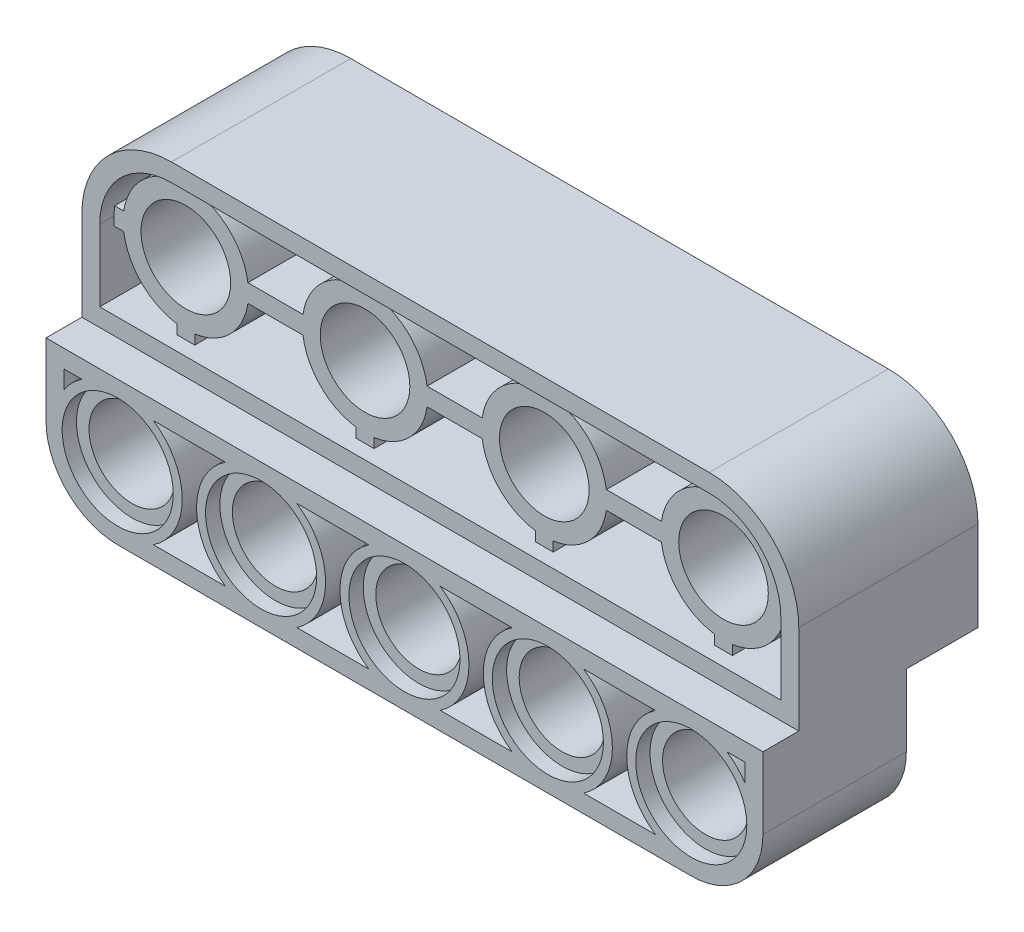
SolidWorks part; units mm, degrees
ref_plane "Front Plane" through (0, 0, 0) normal (0, 0, 1) x (1, 0, 0)
ref_plane "Top Plane" through (0, 0, 0) normal (0, 1, 0) x (1, 0, 0)
ref_plane "Right Plane" through (0, 0, 0) normal (1, 0, 0) x (0, 0, -1)
sketch "Sketch1" plane through (0, 0, 0) normal (1, 0, 0) x (0, 0, -1)
  line L0 (-5, -5) -> (-5, -13)
  line L1 (5, 5) -> (-5, 5)
  line L2 (5, 5) -> (5, -5)
  line L3 (5, -5) -> (-5, -5)
  line L4 (-5, 5) -> (-5, -5)
  line L5 (5, 5) -> (-5, -5) construction
  line L6 (5, -5) -> (-5, 5) construction
  line L7 (-5, -13) -> (3, -13)
  line L8 (3, -13) -> (3, -5)
  point P0 (0, 0)
  dimension "D1" = 10
  dimension "D2" = 10
  dimension "D3" = 8
  dimension "D4" = 8
extrude "Boss-Extrude1" add sketch "Sketch1" along normal blind 40 contours L1 L4 L3 L2 | L7 L8 L3 L0 region at (0, -9, 1) region at (0, 0, 0)
sketch "Sketch2" plane through (0, 0, -5) normal (0, 0, -1) x (-1, 0, 0)
  line L0 (-40, 0) -> (0, 0) construction
  line L1 (-40, 5) -> (-40, -5) construction
  line L2 (0, 5) -> (0, -5) construction
  line L3 (-35, 0) -> (-35, -7.7251) construction
  line L4 (-35, -7.7251) -> (-25, -7.7251) construction
  line L5 (-25, -7.7251) -> (-25, 0) construction
  line L6 (-25, 0) -> (-25, 7.4414) construction
  line L7 (-25, 7.4414) -> (-15, 7.4414) construction
  line L8 (-15, 7.4414) -> (-15, 0) construction
  line L9 (-15, 0) -> (-15, -7.7251) construction
  line L10 (-15, -7.7251) -> (-5, -7.7251) construction
  line L11 (-5, -7.7251) -> (-5, 0) construction
  circle A0 centre (-35, 0) radius 2.5
  circle A1 centre (-25, 0) radius 2.5
  circle A2 centre (-15, 0) radius 2.5
  circle A3 centre (-5, 0) radius 2.5
  dimension "D2" = 5
  dimension "D1" = 5
  dimension "D3" = 10
extrude "Cut-Extrude1" cut sketch "Sketch2" against normal through all
sketch "Sketch3" plane through (0, 0, -3) normal (0, 0, -1) x (-1, 0, 0)
  line L0 (-40, -9) -> (0, -9) construction
  line L1 (-40, -13) -> (-40, -5) construction
  line L2 (0, -13) -> (0, -5) construction
  line L3 (-40, -13) -> (0, -13) construction
  circle A0 centre (-36, -9) radius 2.4
  circle A1 centre (-28, -9) radius 2.4
  circle A2 centre (-20, -9) radius 2.4
  circle A3 centre (-12, -9) radius 2.4
  circle A4 centre (-4, -9) radius 2.4
  circle A5 centre (-36, -9) radius 4 construction
  circle A6 centre (-4, -9) radius 4 construction
  dimension "D1" = 4.8
  dimension "D2" = 8
  dimension "D3" = 8
  dimension "D4" = 8
  dimension "D5" = 8
extrude "Cut-Extrude2" cut sketch "Sketch3" against normal through all
fillet "Fillet1" radius 5 2 edges at (0, 5, 0) (40, 5, 0)
fillet "Fillet2" radius 4 2 edges at (0, -13, 1) (40, -13, 1)
sketch "Sketch4" plane through (0, 0, -3) normal (0, 0, -1) x (-1, 0, 0)
  circle A0 centre (-36, -9) radius 3.1
  circle A1 centre (-28, -9) radius 3.1
  circle A2 centre (-20, -9) radius 3.1
  circle A3 centre (-12, -9) radius 3.1
  circle A4 centre (-4, -9) radius 3.1
  dimension "D1" = 6.2
  dimension "D3" = 8
  dimension "D2" = 5
extrude "Cut-Extrude3" cut sketch "Sketch4" against normal blind 0.8
sketch "Sketch5" plane through (0, 0, 5) normal (0, 0, 1) x (1, 0, 0)
  circle A1 centre (4, -9) radius 3.1
  circle A2 centre (4, -9) radius 3.1
  circle A3 centre (12, -9) radius 3.1
  circle A4 centre (12, -9) radius 3.1
  circle A5 centre (20, -9) radius 3.1
  circle A6 centre (20, -9) radius 3.1
  circle A7 centre (28, -9) radius 3.1
  circle A8 centre (28, -9) radius 3.1
  circle A9 centre (36, -9) radius 3.1
  circle A10 centre (36, -9) radius 3.1
  dimension "D1" = 0
  dimension "D2" = 0
  dimension "D3" = 0
  dimension "D4" = 0
  dimension "D5" = 0
extrude "Cut-Extrude4" cut sketch "Sketch5" against normal blind 0.8
sketch "Sketch6" plane through (0, 0, -5) normal (0, 0, -1) x (-1, 0, 0)
  circle A2 centre (-25, 0) radius 3.5
  circle A3 centre (-35, 0) radius 3.5
  circle A4 centre (-35, 0) radius 3.5
  circle A5 centre (-15, 0) radius 3.5
  circle A6 centre (-5, 0) radius 3.5
  dimension "D1" = 1
  dimension "D3" = 10
  dimension "D2" = 4
extrude "Cut-Extrude5" cut sketch "Sketch6" against normal blind 0.8
sketch "Sketch7" plane through (0, 0, 5) normal (0, 0, 1) x (1, 0, 0)
  circle A1 centre (5, 0) radius 3.5
  circle A2 centre (5, 0) radius 3.5
  circle A3 centre (15, 0) radius 3.5
  circle A4 centre (15, 0) radius 3.5
  circle A5 centre (35, 0) radius 3.5
  circle A6 centre (35, 0) radius 3.5
  circle A7 centre (25, 0) radius 3.5
  circle A8 centre (25, 0) radius 3.5
  dimension "D1" = 0
  dimension "D2" = 0
  dimension "D3" = 0
  dimension "D4" = 0
extrude "Cut-Extrude6" cut sketch "Sketch7" against normal blind 0.8
sketch "Sketch8" plane through (0, 0, -5) normal (0, 0, -1) x (-1, 0, 0)
  line L1 (-5, 4) -> (-35, 4)
  line L2 (-39, 0) -> (-39, -4)
  line L3 (-39, -4) -> (-1, -4)
  line L4 (-1, -4) -> (-1, 0)
  line L5 (0, -5) -> (0, 0)
  line L6 (-5, 5) -> (-35, 5)
  line L7 (-40, 0) -> (-40, -5)
  line L8 (-40, -5) -> (0, -5)
  line L9 (0, -5) -> (0, 0)
  line L10 (-5, 5) -> (-35, 5)
  line L11 (-40, 0) -> (-40, -5)
  line L12 (-40, -5) -> (0, -5)
  arc A0 (-35, 4) -> (-39, 0) centre (-35, 0) ccw
  arc A1 (-1, 0) -> (-5, 4) centre (-5, 0) ccw
  arc A2 (0, 0) -> (-5, 5) centre (-5, 0) ccw
  arc A3 (-35, 5) -> (-40, 0) centre (-35, 0) ccw
  arc A4 (0, 0) -> (-5, 5) centre (-5, 0) ccw
  arc A5 (-35, 5) -> (-40, 0) centre (-35, 0) ccw
  circle A6 centre (-5, 0) radius 3.5 construction
  circle A7 centre (-15, 0) radius 3.5 construction
  circle A8 centre (-25, 0) radius 3.5 construction
  circle A9 centre (-35, 0) radius 3.5 construction
  circle A10 centre (-5, 0) radius 3.5
  circle A11 centre (-15, 0) radius 3.5
  circle A12 centre (-25, 0) radius 3.5
  circle A13 centre (-35, 0) radius 3.5
  circle M13 centre (-5, 0) radius 3.5
  circle M14 centre (-35, 0) radius 3.5
  circle M15 centre (-15, 0) radius 3.5
  circle M16 centre (-25, 0) radius 3.5
  dimension "D1" = 0
  dimension "D2" = 1
extrude "Cut-Extrude7" cut sketch "Sketch8" against normal blind 4.5 contours L4 A1 L1 A0 L2 L3 M13 M15 M16 M14 region at (20, -0.149, -5)
sketch "Sketch9" plane through (0, 0, 5) normal (0, 0, 1) x (1, 0, 0)
  line L4 (0, 0) -> (0, -5)
  line L5 (35, 5) -> (5, 5)
  line L6 (40, -5) -> (40, 0)
  line L7 (0, -5) -> (40, -5)
  line L8 (0, 0) -> (0, -5)
  line L9 (35, 5) -> (5, 5)
  line L10 (40, -5) -> (40, 0)
  line L11 (0, -5) -> (40, -5)
  line L12 (35, 4) -> (5, 4)
  line L13 (39, -4) -> (39, 0)
  line L14 (1, -4) -> (39, -4)
  line L15 (1, 0) -> (1, -4)
  line L16 (35, 4) -> (5, 4)
  line L17 (39, -4) -> (39, 0)
  line L18 (1, -4) -> (39, -4)
  line L19 (1, 0) -> (1, -4)
  circle A1 centre (35, 0) radius 3.5
  arc A2 (5, 5) -> (0, 0) centre (5, 0) ccw
  arc A3 (40, 0) -> (35, 5) centre (35, 0) ccw
  arc A4 (5, 5) -> (0, 0) centre (5, 0) ccw
  arc A5 (40, 0) -> (35, 5) centre (35, 0) ccw
  arc A6 (39, 0) -> (35, 4) centre (35, 0) ccw
  arc A7 (5, 4) -> (1, 0) centre (5, 0) ccw
  arc A8 (39, 0) -> (35, 4) centre (35, 0) ccw
  arc A9 (5, 4) -> (1, 0) centre (5, 0) ccw
  circle A10 centre (35, 0) radius 3.5
  circle A11 centre (25, 0) radius 3.5
  circle A12 centre (25, 0) radius 3.5
  circle A13 centre (15, 0) radius 3.5
  circle A14 centre (15, 0) radius 3.5
  circle A15 centre (5, 0) radius 3.5
  circle A16 centre (5, 0) radius 3.5
  circle M17 centre (5, 0) radius 3.5
  circle M18 centre (25, 0) radius 3.5
  circle M19 centre (35, 0) radius 3.5
  circle M20 centre (15, 0) radius 3.5
  dimension "D1" = 0
  dimension "D2" = 0
  dimension "D3" = 0
  dimension "D4" = 0
  dimension "D5" = 0
  dimension "D6" = 0
extrude "Cut-Extrude8" cut sketch "Sketch9" against normal blind 4.5 contours L16 A9 L19 L18 L17 A8 M18 M20 M19 M17 region at (20, -0.149, 5)
sketch "Sketch10" plane through (0, 0, -3) normal (0, 0, -1) x (-1, 0, 0)
  line L2 (-36, -12) -> (-4, -12)
  line L3 (-36, -12) -> (-4, -12)
  line L4 (-40, -5) -> (0, -5) construction
  line L5 (-39, -9) -> (-39, -5)
  line L6 (-39, -9) -> (-39, -5)
  line L7 (-40, -5) -> (0, -5)
  line L8 (0, -9) -> (0, -5) construction
  line L9 (0, -9) -> (0, -5)
  line L10 (-1, -9) -> (-1, -5)
  line L11 (-40, -6) -> (0, -6)
  circle A0 centre (-36, -9) radius 3.6
  circle A1 centre (-28, -9) radius 3.6
  circle A2 centre (-20, -9) radius 3.6
  circle A3 centre (-12, -9) radius 3.6
  circle A4 centre (-4, -9) radius 3.6
  dimension "D1" = 7.2
  dimension "D5" = 8
  dimension "D6" = 1
  dimension "D2" = 1
  dimension "D3" = 1
  dimension "D7" = 1
  dimension "D4" = 5
extrude "Cut-Extrude9" cut sketch "Sketch10" against normal blind 3.5 contours A1 L11 A0 L3 | A2 L11 A1 L3 | A3 L11 A2 L3 | A4 L11 A3 L3 | A0 L11 L6 | A4 L10 L11 region at (32, -9, -3) region at (38.6862, -6.3138, -3) region at (24, -9, -3) region at (16, -9, -3) region at (1.3138, -6.3138, -3) region at (8, -9, -3)
sketch "Sketch11" plane through (0, 0, 5) normal (0, 0, 1) x (1, 0, 0)
  line L0 (40, -5) -> (0, -5) construction
  line L1 (0, -9) -> (0, -5) construction
  line L2 (39, -9) -> (39, -5) construction
  line L3 (36, -12) -> (4, -12) construction
  line L4 (40, -6) -> (0, -6) construction
  line L5 (1, -9) -> (1, -5) construction
  line L6 (40, -5) -> (0, -5)
  line L7 (0, -9) -> (0, -5)
  line L8 (39, -9) -> (39, -5)
  line L9 (36, -12) -> (4, -12)
  line L10 (40, -6) -> (0, -6)
  line L11 (1, -9) -> (1, -5)
  circle A1 centre (12, -9) radius 3.6
  circle A2 centre (12, -9) radius 3.6
  circle A3 centre (20, -9) radius 3.6
  circle A4 centre (20, -9) radius 3.6
  circle A5 centre (28, -9) radius 3.6
  circle A6 centre (28, -9) radius 3.6
  circle A7 centre (36, -9) radius 3.6
  circle A8 centre (36, -9) radius 3.6
  circle A9 centre (4, -9) radius 3.6
  circle A10 centre (4, -9) radius 3.6
  dimension "D1" = 0
  dimension "D2" = 0
  dimension "D3" = 0
  dimension "D4" = 0
  dimension "D5" = 0
extrude "Cut-Extrude10" cut sketch "Sketch11" against normal blind 3.5 contours A10 L9 A2 L10 | A4 L10 A2 L9 | A6 L10 A4 L9 | A8 L10 A6 L9 | A8 L8 L10 | A10 L10 L11 region at (38.6862, -6.3138, 5) region at (1.3138, -6.3138, 5) region at (32, -9, 5) region at (8, -9, 5) region at (24, -9, 5) region at (16, -9, 5)
sketch "Sketch12" plane through (0, 0, -4.2) normal (0, 0, -1) x (-1, 0, 0)
  line L1 (-39, 0) -> (2.7351, 0) construction
  line L2 (-39, -0.5) -> (2.7351, -0.5)
  line L3 (-39, 0.5) -> (2.7351, 0.5)
  line L4 (-35, 4) -> (-35, -4) construction
  line L5 (-1, -4) -> (-1, 0)
  line L6 (-39, -4) -> (-1, -4)
  line L7 (-39, 0) -> (-39, -4)
  line L8 (-5, 4) -> (-35, 4)
  line L9 (-1, -4) -> (-1, 0)
  line L10 (-39, -4) -> (-1, -4)
  line L11 (-39, 0) -> (-39, -4)
  line L12 (-5, 4) -> (-35, 4)
  line L13 (-35.5, 4) -> (-35.5, -4)
  line L14 (-34.5, 4) -> (-34.5, -4)
  line L15 (-24.5, 4) -> (-24.5, -4)
  line L16 (-25.5, 4) -> (-25.5, -4)
  line L17 (-14.5, 4) -> (-14.5, -4)
  line L18 (-15.5, 4) -> (-15.5, -4)
  line L19 (-4.5, 4) -> (-4.5, -4)
  line L20 (-5.5, 4) -> (-5.5, -4)
  circle A0 centre (-5, 0) radius 3.5 construction
  circle A1 centre (-15, 0) radius 3.5 construction
  circle A2 centre (-25, 0) radius 3.5 construction
  circle A3 centre (-35, 0) radius 3.5 construction
  circle A4 centre (-5, 0) radius 3.5
  circle A5 centre (-15, 0) radius 3.5
  circle A6 centre (-25, 0) radius 3.5
  circle A7 centre (-35, 0) radius 3.5
  arc A10 (-35, 4) -> (-39, 0) centre (-35, 0) ccw
  arc A11 (-1, 0) -> (-5, 4) centre (-5, 0) ccw
  arc A12 (-35, 4) -> (-39, 0) centre (-35, 0) ccw
  arc A13 (-1, 0) -> (-5, 4) centre (-5, 0) ccw
  circle M14 centre (-35, 0) radius 3.5
  dimension "D7" = 10
  dimension "D1" = 0
  dimension "D2" = 0.5
  dimension "D3" = 0.5
  dimension "D4" = 0.5
  dimension "D5" = 0.5
  dimension "D6" = 4
extrude "Boss-Extrude2" add sketch "Sketch12" against normal up to surface (3.7 mm away) contours A6 L3 L2 M14 | A6 L2 A5 L3 | A6 L15 L12 L16 | L12 A12 L13 L14 M14 | L3 A12 L11 L2 M14 | A6 L16 L10 L15 | L14 L13 L10 M14 | A5 L18 L10 L17 | A5 L17 L12 L18 | A5 L2 A4 L3 | L19 A13 L12 L20 A4 | A4 L20 L10 L19 | L9 A13 L3 A4 L2 region at (38.7414, -0.0039, -4.2) region at (35, -3.7439, -4.2) region at (34.9961, 3.7414, -4.2) region at (30, 0, -4.2) region at (25, -3.7439, -4.2) region at (25, 3.7439, -4.2) region at (15, -3.7439, -4.2) region at (20, 0, -4.2) region at (15, 3.7439, -4.2) region at (5, -3.7439, -4.2) region at (10, 0, -4.2) region at (5.0039, 3.7414, -4.2) region at (1.2586, -0.0039, -4.2) up to face at (5, 3.5, -0.5)
sketch "Sketch13" plane through (0, 0, 4.2) normal (0, 0, 1) x (1, 0, 0)
  line L0 (39, -0.5) -> (-2.7351, -0.5) construction
  line L1 (25.5, 4) -> (25.5, -4) construction
  line L2 (34.5, 4) -> (34.5, -4) construction
  line L3 (35.5, 4) -> (35.5, -4) construction
  line L4 (39, -4) -> (39, 0)
  line L5 (35, 4) -> (5, 4)
  line L6 (1, 0) -> (1, -4)
  line L7 (1, -4) -> (39, -4)
  line L8 (39, -4) -> (39, 0)
  line L9 (35, 4) -> (5, 4)
  line L10 (1, 0) -> (1, -4)
  line L11 (1, -4) -> (39, -4)
  line L12 (39, 0.5) -> (-2.7351, 0.5) construction
  line L13 (5.5, 4) -> (5.5, -4) construction
  line L14 (4.5, 4) -> (4.5, -4) construction
  line L15 (15.5, 4) -> (15.5, -4) construction
  line L16 (14.5, 4) -> (14.5, -4) construction
  line L17 (24.5, 4) -> (24.5, -4) construction
  line L18 (39, -0.5) -> (-2.7351, -0.5)
  line L19 (25.5, 4) -> (25.5, -4)
  line L20 (34.5, 4) -> (34.5, -4)
  line L21 (35.5, 4) -> (35.5, -4)
  line L22 (39, 0.5) -> (-2.7351, 0.5)
  line L23 (5.5, 4) -> (5.5, -4)
  line L24 (4.5, 4) -> (4.5, -4)
  line L25 (15.5, 4) -> (15.5, -4)
  line L26 (14.5, 4) -> (14.5, -4)
  line L27 (24.5, 4) -> (24.5, -4)
  circle A1 centre (35, 0) radius 3.5
  circle A2 centre (35, 0) radius 3.5
  circle A3 centre (25, 0) radius 3.5
  circle A4 centre (25, 0) radius 3.5
  circle A5 centre (15, 0) radius 3.5
  circle A6 centre (15, 0) radius 3.5
  circle A7 centre (5, 0) radius 3.5
  circle A8 centre (5, 0) radius 3.5
  arc A10 (39, 0) -> (35, 4) centre (35, 0) ccw
  arc A11 (5, 4) -> (1, 0) centre (5, 0) ccw
  arc A12 (39, 0) -> (35, 4) centre (35, 0) ccw
  arc A13 (5, 4) -> (1, 0) centre (5, 0) ccw
  circle M11 centre (15, 0) radius 3.5
  dimension "D1" = 0
  dimension "D2" = 0
  dimension "D3" = 0
  dimension "D4" = 0
  dimension "D5" = 0
extrude "Boss-Extrude3" add sketch "Sketch13" against normal up to surface (3.7 mm away) contours L9 L26 L25 M11 | L9 A13 L24 A8 L23 | L22 A13 L10 L18 A8 | A8 L24 L11 L23 | A8 L18 L22 M11 | L26 L11 L25 M11 | A4 L22 L18 M11 | A4 L19 L9 L27 | A4 L18 A2 L22 | A4 L27 L11 L19 | L21 A12 L9 L20 A2 | L8 A12 L22 A2 L18 | A2 L20 L11 L21 region at (38.7414, -0.0039, 4.2) region at (35, -3.7439, 4.2) region at (25, -3.7439, 4.2) region at (34.9961, 3.7414, 4.2) region at (30, 0, 4.2) region at (15, -3.7439, 4.2) region at (20, 0, 4.2) region at (25, 3.7439, 4.2) region at (5, -3.7439, 4.2) region at (10, 0, 4.2) region at (15, 3.7439, 4.2) region at (1.2586, -0.0039, 4.2) region at (5.0039, 3.7414, 4.2) up to face at (28.5, 0, 0.5)
sketch "Sketch14" plane through (0, 0, -3) normal (0, 0, -1) x (-1, 0, 0)
  line L1 (-39, -6) -> (-39, -5)
  line L2 (-40, -5) -> (0, -5) construction
  line L3 (-39, -6) -> (-37.99, -6)
  line L4 (-37.99, -6) -> (-37.99, -5)
  line L5 (-37.99, -5) -> (-39, -5)
  line L6 (-34.01, -6) -> (-34.01, -5)
  line L7 (-40, -5) -> (0, -5) construction
  line L8 (-34.01, -6) -> (-29.99, -6)
  line L9 (-29.99, -6) -> (-29.99, -5)
  line L10 (-29.99, -5) -> (-34.01, -5)
  line L11 (-26.01, -6) -> (-26.01, -5)
  line L12 (-26.01, -6) -> (-21.99, -6)
  line L13 (-21.99, -6) -> (-21.99, -5)
  line L14 (-21.99, -5) -> (-26.01, -5)
  line L15 (-18.01, -6) -> (-18.01, -5)
  line L16 (-18.01, -6) -> (-13.99, -6)
  line L17 (-13.99, -6) -> (-13.99, -5)
  line L18 (-13.99, -5) -> (-18.01, -5)
  line L19 (-10.01, -6) -> (-10.01, -5)
  line L20 (-10.01, -6) -> (-5.99, -6)
  line L21 (-5.99, -6) -> (-5.99, -5)
  line L22 (-5.99, -5) -> (-10.01, -5)
  line L23 (-1, -6) -> (-2.01, -6)
  line L24 (-2.01, -6) -> (-2.01, -5)
  line L25 (-2.01, -5) -> (-1, -5)
  line L26 (-1, -5) -> (-1, -6)
  dimension "D1" = 4
  dimension "D2" = 8
extrude "Cut-Extrude11" [suppressed] cut sketch "Sketch14" against normal up to surface (3.5 mm away)
sketch "Sketch15" plane through (0, 0, 5) normal (0, 0, 1) x (1, 0, 0)
  line L4 (34.01, -6) -> (34.01, -5)
  line L5 (34.01, -5) -> (29.99, -5)
  line L6 (29.99, -5) -> (29.99, -6)
  line L7 (29.99, -6) -> (34.01, -6)
  line L8 (34.01, -6) -> (34.01, -5)
  line L9 (34.01, -5) -> (29.99, -5)
  line L10 (29.99, -5) -> (29.99, -6)
  line L11 (29.99, -6) -> (34.01, -6)
  line L12 (39, -6) -> (39, -5)
  line L13 (39, -5) -> (37.99, -5)
  line L14 (37.99, -5) -> (37.99, -6)
  line L15 (37.99, -6) -> (39, -6)
  line L16 (39, -6) -> (39, -5)
  line L17 (39, -5) -> (37.99, -5)
  line L18 (37.99, -5) -> (37.99, -6)
  line L19 (37.99, -6) -> (39, -6)
  line L20 (10.01, -6) -> (10.01, -5)
  line L21 (10.01, -5) -> (5.99, -5)
  line L22 (5.99, -5) -> (5.99, -6)
  line L23 (5.99, -6) -> (10.01, -6)
  line L24 (10.01, -6) -> (10.01, -5)
  line L25 (10.01, -5) -> (5.99, -5)
  line L26 (5.99, -5) -> (5.99, -6)
  line L27 (5.99, -6) -> (10.01, -6)
  line L28 (18.01, -6) -> (18.01, -5)
  line L29 (18.01, -5) -> (13.99, -5)
  line L30 (13.99, -5) -> (13.99, -6)
  line L31 (13.99, -6) -> (18.01, -6)
  line L32 (18.01, -6) -> (18.01, -5)
  line L33 (18.01, -5) -> (13.99, -5)
  line L34 (13.99, -5) -> (13.99, -6)
  line L35 (13.99, -6) -> (18.01, -6)
  line L36 (26.01, -6) -> (26.01, -5)
  line L37 (26.01, -5) -> (21.99, -5)
  line L38 (21.99, -5) -> (21.99, -6)
  line L39 (21.99, -6) -> (26.01, -6)
  line L40 (26.01, -6) -> (26.01, -5)
  line L41 (26.01, -5) -> (21.99, -5)
  line L42 (21.99, -5) -> (21.99, -6)
  line L43 (21.99, -6) -> (26.01, -6)
  line L44 (2.01, -5) -> (1, -5)
  line L45 (1, -5) -> (1, -6)
  line L46 (1, -6) -> (2.01, -6)
  line L47 (2.01, -6) -> (2.01, -5)
  line L48 (2.01, -5) -> (1, -5)
  line L49 (1, -5) -> (1, -6)
  line L50 (1, -6) -> (2.01, -6)
  line L51 (2.01, -6) -> (2.01, -5)
  dimension "D1" = 0
  dimension "D2" = 0
  dimension "D3" = 0
  dimension "D4" = 0
  dimension "D5" = 0
  dimension "D6" = 0
extrude "Cut-Extrude12" [suppressed] cut sketch "Sketch15" against normal up to surface (3.5 mm away)
ref_plane "Plane1" through (0, -5, 0) normal (0, -1, 0) x (-1, 0, 0)
split "Split1" trim tools "Plane1" bodies to split 113 resulting bodies 116 117
move or copy body "Body-Move/Copy1" bodies to move or copy 117 copy no translate (0, 0, -2)
combine bodies "Combine1" operation type add bodies to combine 116 118
